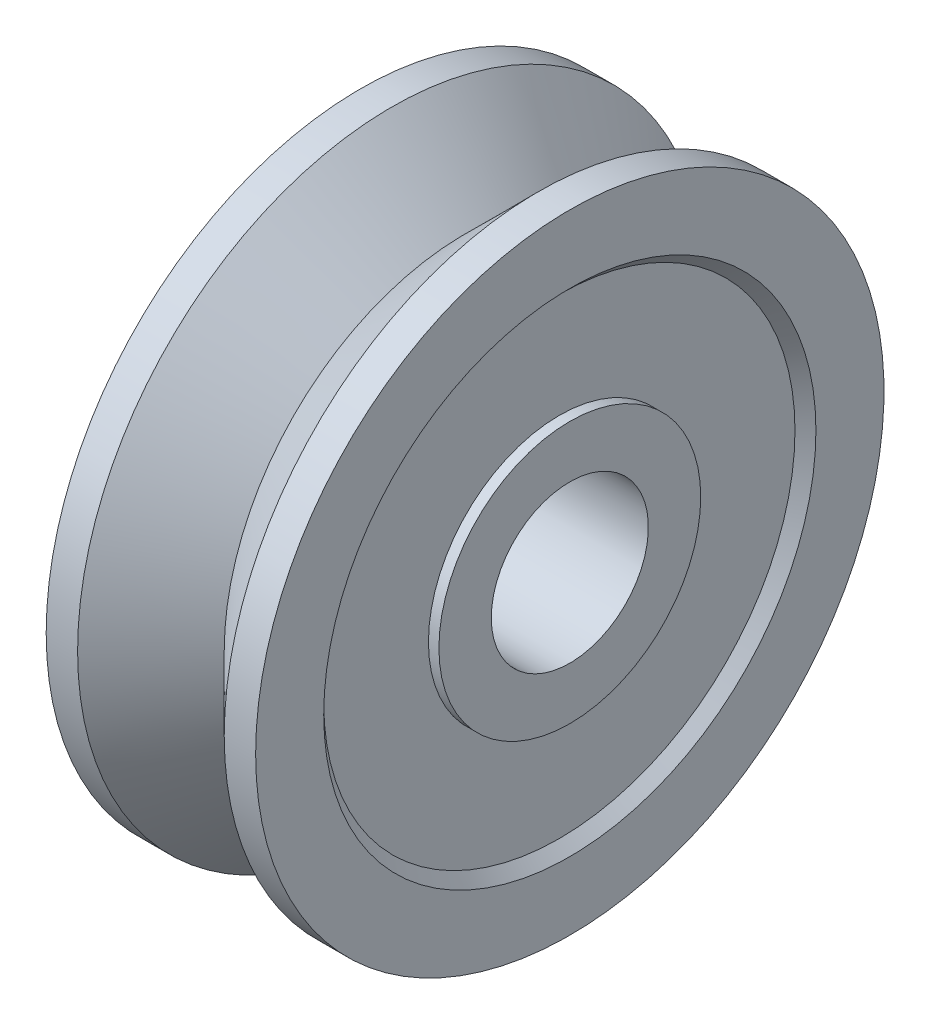
SolidWorks part; units mm, degrees
material "合金钢 (SS)"
ref_plane "前视基准面" through (0, 0, 0) normal (0, 0, 1) x (1, 0, 0)
ref_plane "上视基准面" through (0, 0, 0) normal (0, 1, 0) x (1, 0, 0)
ref_plane "右视基准面" through (0, 0, 0) normal (1, 0, 0) x (0, 0, -1)
sketch "草图1" plane through (0, 0, 0) normal (0, 0, 1) x (1, 0, 0)
  line L0 (0, 0) -> (2, 0) construction
  line L1 (2, 0) -> (2, 1.5) construction
  line L2 (2, 1.5) -> (-2, 1.5) construction
  line L3 (-2, 1.5) -> (-2, 0) construction
  line L4 (-2, 0) -> (0, 0) construction
  line L5 (-2, 1.5) -> (-2, 6)
  line L6 (-2, 6) -> (-1.4, 6)
  line L7 (-1.4, 6) -> (0, 4.6)
  line L8 (0, 4.6) -> (1.4, 6)
  line L9 (1.4, 6) -> (2, 6)
  line L10 (2, 6) -> (2, 1.5)
  line L11 (2, 1.5) -> (-2, 1.5)
  point P9 (0, 0)
  point P13 (1.3725, 6.1176)
  dimension "D1" = 2
  dimension "D2" = 2
  dimension "D3" = 1.5
  dimension "D4" = 4.5
  dimension "D5" = 0.6
  dimension "D6" = 0.6
  dimension "D7" = 4.5
  dimension "D8" = 1.4
  dimension "D9" = 1.4
revolve "旋转1" add sketch "草图1" angle 360 about L4
sketch "草图2" plane through (2, 0, 0) normal (1, 0, 0) x (0, 0, -1)
  circle A0 centre (0, 0) radius 2.5
  circle A1 centre (0, 0) radius 4.5
  dimension "D1" = 5
  dimension "D2" = 9
extrude "切除-拉伸1" cut sketch "草图2" against normal blind 0.2
chamfer "倒角1" distance 0.2 angle 45 1 edges at (2, 0, -4.5)
sketch "草图3" plane through (-2, 0, 0) normal (-1, 0, 0) x (0, 0, 1)
  circle A0 centre (0, 0) radius 2.5
  circle A1 centre (0, 0) radius 4.5
  dimension "D1" = 5
  dimension "D2" = 9
extrude "切除-拉伸2" cut sketch "草图3" against normal blind 0.2
chamfer "倒角2" distance 0.2 angle 45 1 edges at (-2, 0, 4.5)
